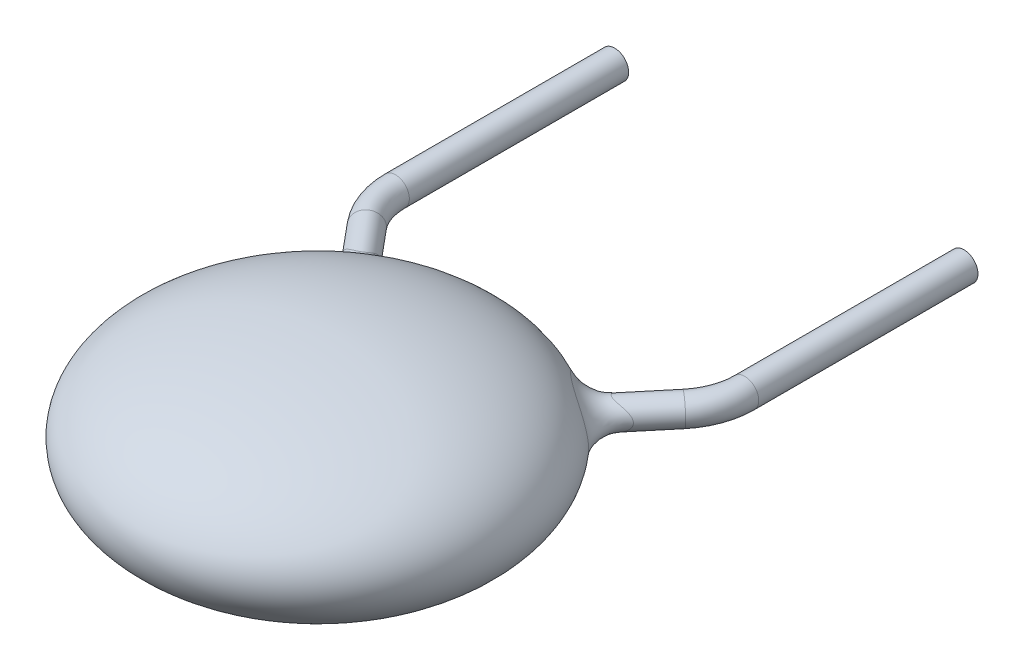
SolidWorks part; units mm, degrees
ref_plane "Front Plane" through (0, 0, 0) normal (0, 0, 1) x (1, 0, 0)
ref_plane "Top Plane" through (0, 0, 0) normal (0, 1, 0) x (1, 0, 0)
ref_plane "Right Plane" through (0, 0, 0) normal (1, 0, 0) x (0, 0, -1)
sketch "Sketch3" plane through (0, 0, 0) normal (1, 0, 0) x (0, 0, -1)
  line L7 (-4.75, 1.25) -> (-4.75, -1.25)
  ellipse E0 centre (-4.75, 0) end of major axis (-2, 0) minor radius 1.25 (-4.75, 1.25) -> (-4.75, -1.25) cw
  point P1 (0, 0)
  point P11 (-4.5, 0)
  dimension "D1" = 5.5
  dimension "D2" = 2.5
  dimension "D3" = 2
revolve "Revolve1" add sketch "Sketch3" angle 360 mid plane about L7
sketch "Sketch149" plane through (0, 0, 0) normal (0, 0, 1) x (1, 0, 0)
  line L0 (-2.5, 0) -> (2.5, 0) construction
  circle A0 centre (-2.5, 0) radius 0.2
  point P2 (0, 0)
  point P4 (0, 0)
  point P7 (0, 0)
  dimension "D3" = 0.4
  dimension "D1" = 5
sketch "Sketch150" plane through (0, 0, 0) normal (0, 1, 0) x (1, 0, 0)
  line L0 (-2.5, 2) -> (-2.5, -1.138)
  line L2 (-2.2682, -1.7781) -> (0, -4.5)
  line L3 (0, -4.5) -> (2.2682, -1.7781)
  line L4 (2.5, -1.138) -> (2.5, 2)
  arc A0 (2.2682, -1.7781) -> (2.5, -1.138) centre (1.5, -1.138) ccw
  arc A1 (-2.5, -1.138) -> (-2.2682, -1.7781) centre (-1.5, -1.138) ccw
  point P2 (-1.0516, 0.5518)
  point P3 (0, 0)
  point P7 (0, 0)
  point P9 (0, 0)
  point P13 (0, 0)
  point P15 (-1.25, -1.2969)
  point P19 (2.5, -1.5)
  point P22 (-2.5, -1.5)
  dimension "D3" = 1
  dimension "D1" = 2
  dimension "D2" = 0.5
sweep "Sweep1" add profiles "Sketch149" path "Sketch150"
fillet "Fillet1" radius 0.5 2 edges at (1.4709, 0.0368, 2.4279) (-1.4709, -0.0368, 2.4279)
